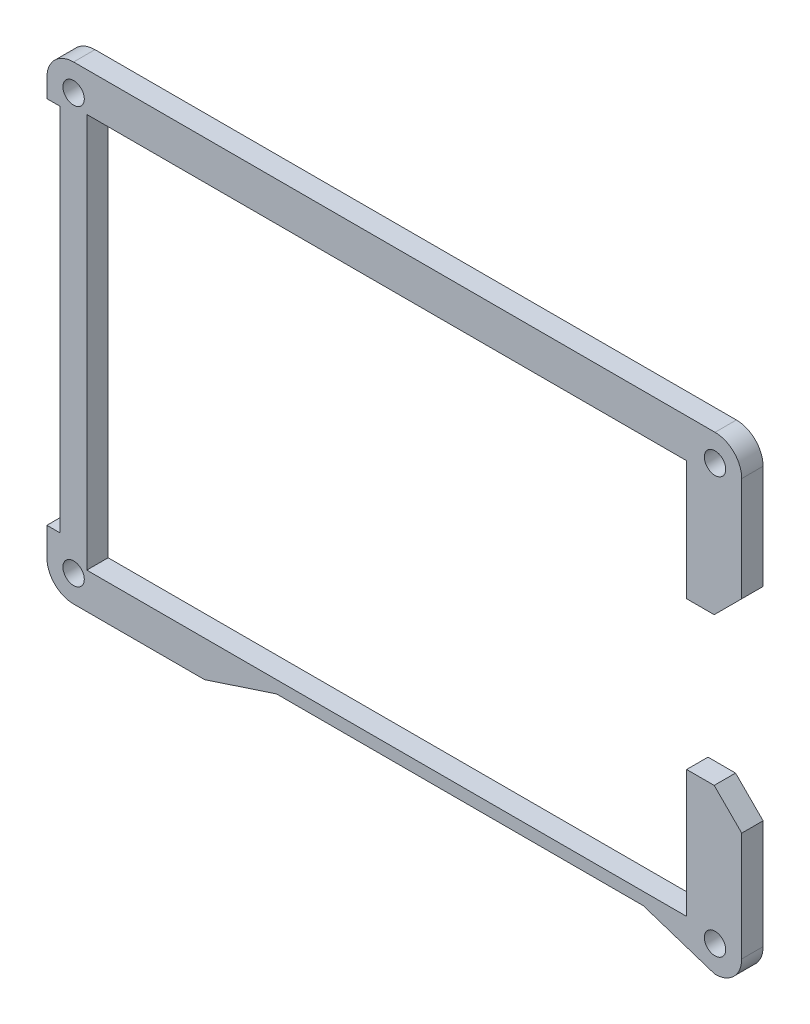
SolidWorks part; units mm, degrees
ref_plane "Front Plane" through (0, 0, 0) normal (0, 0, 1) x (1, 0, 0)
ref_plane "Top Plane" through (0, 0, 0) normal (0, 1, 0) x (1, 0, 0)
ref_plane "Right Plane" through (0, 0, 0) normal (1, 0, 0) x (0, 0, -1)
sketch "Sketch1" plane through (0, 0, 0) normal (0, 0, 1) x (1, 0, 0)
  line L0 (-401.0571, 148.341) -> (-380.1672, 148.341)
  line L1 (-399.1521, 148.341) -> (-399.1521, 95.6449)
  line L2 (-395.3675, 92.9525) -> (-395.3675, 149.2432)
  line L3 (-395.3675, 149.2432) -> (-309.8086, 149.2432)
  line L4 (-395.3675, 92.9525) -> (-309.8086, 92.9525)
  line L5 (-309.8086, 149.2432) -> (-309.8086, 92.9525)
  line L6 (-309.8086, 128.8851) -> (-321.2743, 128.8851)
  line L7 (-321.2743, 128.8851) -> (-321.2743, 115.6771)
  line L8 (-321.2743, 115.6771) -> (-309.8086, 115.6771)
  line L9 (-309.8086, 128.8851) -> (-305.8779, 128.8851)
  line L10 (-375.4172, 95.6449) -> (-401.0571, 95.6449)
  line L11 (-401.0571, 150.9566) -> (-401.0571, 148.341) construction
  line L12 (-305.7573, 154.7804) -> (-397.2471, 154.7804) construction
  line L13 (-301.9473, 91.6317) -> (-301.9473, 150.9704) construction
  line L14 (-315.9973, 91.1883) -> (-305.7573, 87.8217) construction
  line L15 (-315.9973, 91.1883) -> (-368.3165, 91.1883) construction
  line L16 (-368.3165, 91.1883) -> (-378.5565, 87.8217) construction
  line L17 (-378.5565, 87.8217) -> (-397.2472, 87.8217) construction
  line L18 (-401.0571, 95.6449) -> (-401.0571, 91.6593) construction
  line L19 (-401.0571, 150.9566) -> (-401.0571, 148.341)
  line L20 (-305.7573, 154.7804) -> (-397.2471, 154.7804)
  line L21 (-301.9473, 91.6317) -> (-301.9473, 150.9704)
  line L22 (-315.9973, 91.1883) -> (-305.7573, 87.8217)
  line L23 (-315.9973, 91.1883) -> (-368.3165, 91.1883)
  line L24 (-368.3165, 91.1883) -> (-378.5565, 87.8217)
  line L25 (-378.5565, 87.8217) -> (-397.2472, 87.8217)
  line L26 (-401.0571, 95.6449) -> (-401.0571, 91.6593)
  line L27 (-305.8779, 128.8851) -> (-301.9473, 132.8158)
  line L28 (-309.8086, 115.6771) -> (-305.8779, 115.6771)
  line L29 (-305.8779, 115.6771) -> (-301.9473, 111.7464)
  line L30 (-309.8086, 141.4927) -> (-301.9473, 141.4927) construction
  line L31 (-305.878, 141.4927) -> (-305.8779, 128.8851) construction
  arc A0 (-397.2471, 154.7804) -> (-401.0571, 150.9566) centre (-397.2471, 150.9704) ccw construction
  arc A1 (-301.9473, 150.9704) -> (-305.7573, 154.7804) centre (-305.7573, 150.9704) ccw construction
  arc A2 (-305.7573, 87.8217) -> (-301.9473, 91.6317) centre (-305.7573, 91.6317) ccw construction
  arc A3 (-401.0571, 91.6593) -> (-397.2472, 87.8217) centre (-397.2472, 91.6317) ccw construction
  arc A4 (-397.2471, 154.7804) -> (-401.0571, 150.9566) centre (-397.2471, 150.9704) ccw
  arc A5 (-301.9473, 150.9704) -> (-305.7573, 154.7804) centre (-305.7573, 150.9704) ccw
  arc A6 (-305.7573, 87.8217) -> (-301.9473, 91.6317) centre (-305.7573, 91.6317) ccw
  arc A7 (-401.0571, 91.6593) -> (-397.2472, 87.8217) centre (-397.2472, 91.6317) ccw
  circle A8 centre (-397.2471, 150.9704) radius 1.3462 construction
  circle A9 centre (-305.7573, 150.9704) radius 1.3462 construction
  circle A10 centre (-305.7573, 91.6317) radius 1.3462 construction
  circle A11 centre (-397.2472, 91.6317) radius 1.3462 construction
  circle A12 centre (-397.2471, 150.9704) radius 1.3462
  circle A13 centre (-305.7573, 150.9704) radius 1.3462
  circle A14 centre (-305.7573, 91.6317) radius 1.3462
  circle A15 centre (-397.2472, 91.6317) radius 1.3462
  dimension "D1" = 1.905
  dimension "D2" = 5.6896
  dimension "D3" = 5.5372
  dimension "D4" = 5.1308
  dimension "D5" = 7.8613
  dimension "D6" = 25.8953
  dimension "D7" = 13.208
  dimension "D8" = 11.4657
  dimension "D9" = 45
  dimension "D10" = 45
extrude "Boss-Extrude1" add sketch "Sketch1" along normal blind 3.048 contours L21 A5 L20 A4 L19 L0 L2 L3 L5 L9 L27 A13 A12 | L10 L2 L0 L1 | L26 A7 L25 L24 L23 L22 A6 L21 L29 L28 L5 L4 L2 L10 A15 A14 region at (-400.0327, 149.6488, 0) region at (-397.2598, 121.993, 0) region at (-397.2598, 94.6154, 0)
sketch "Sketch2" plane through (0, 0, 0) normal (0, 0, -1) x (-1, 0, 0)
  circle A0 centre (305.7573, 150.9704) radius 1.524
  circle A1 centre (305.7573, 91.6317) radius 1.524
  circle A2 centre (397.2472, 91.6317) radius 1.524
  circle A3 centre (397.2471, 150.9704) radius 1.524
  dimension "D1" = 3.048
extrude "Cut-Extrude1" cut sketch "Sketch2" against normal through all
sketch "Sketch3" plane through (0, 0, 3.048) normal (0, 0, 1) x (1, 0, 0)
  line L0 (-309.8086, 128.8851) -> (-305.8779, 128.8851) construction
  line L1 (-305.8779, 128.8851) -> (-301.9473, 132.8157) construction
  line L2 (-309.8086, 115.6771) -> (-305.8779, 115.6771) construction
  line L3 (-305.8779, 115.6771) -> (-301.9473, 111.7465) construction
  line L4 (-309.8086, 128.8851) -> (-305.8779, 128.8851)
  line L5 (-305.8779, 128.8851) -> (-301.9473, 132.8157)
  line L6 (-309.8086, 115.6771) -> (-305.8779, 115.6771)
  line L7 (-305.8779, 115.6771) -> (-301.9473, 111.7465)
  line L8 (-309.8086, 132.1871) -> (-305.8779, 132.1871)
  line L9 (-309.8086, 149.2432) -> (-309.8086, 128.8851) construction
  line L10 (-305.8779, 132.1871) -> (-301.9473, 136.1177)
  line L11 (-301.9473, 132.8157) -> (-301.9473, 150.9704) construction
  line L12 (-309.8086, 132.1871) -> (-309.8086, 128.8851)
  line L13 (-301.9473, 136.1177) -> (-301.9473, 132.8157)
  line L14 (-309.8086, 115.6771) -> (-309.8086, 111.1051)
  line L15 (-309.8086, 115.6771) -> (-309.8086, 92.9525) construction
  line L16 (-309.8086, 111.1051) -> (-305.8779, 111.1051)
  line L17 (-305.8779, 111.1051) -> (-301.9473, 107.1745)
  line L18 (-301.9473, 91.6317) -> (-301.9473, 111.7465) construction
  line L19 (-301.9473, 107.1745) -> (-301.9473, 111.7465)
  line L20 (-301.9473, 136.1177) -> (-301.9473, 132.8157)
  line L21 (-301.9473, 111.7465) -> (-301.9473, 107.1745)
  line M5 (-301.9473, 132.8157) -> (-301.9473, 150.9704)
  line M20 (-301.9473, 91.6317) -> (-301.9473, 111.7465)
  line M21 (-301.9473, 111.7465) -> (-305.8779, 115.6771)
  line M22 (-305.8779, 115.6771) -> (-309.8086, 115.6771)
  line M23 (-309.8086, 115.6771) -> (-309.8086, 92.9525)
  line M27 (-309.8086, 149.2432) -> (-309.8086, 128.8851)
  line M28 (-309.8086, 128.8851) -> (-305.8779, 128.8851)
  line M29 (-305.8779, 128.8851) -> (-301.9473, 132.8157)
  dimension "D1" = 17.78
  dimension "D2" = 16.51
extrude "Cut-Extrude2" cut sketch "Sketch3" against normal through all contours L10 L8 M27 M28 M29 M5 | L16 L17 M20 M21 M22 M23 region at (-305.878, 131.5188, 3.048) region at (-305.878, 112.4084, 3.048)
